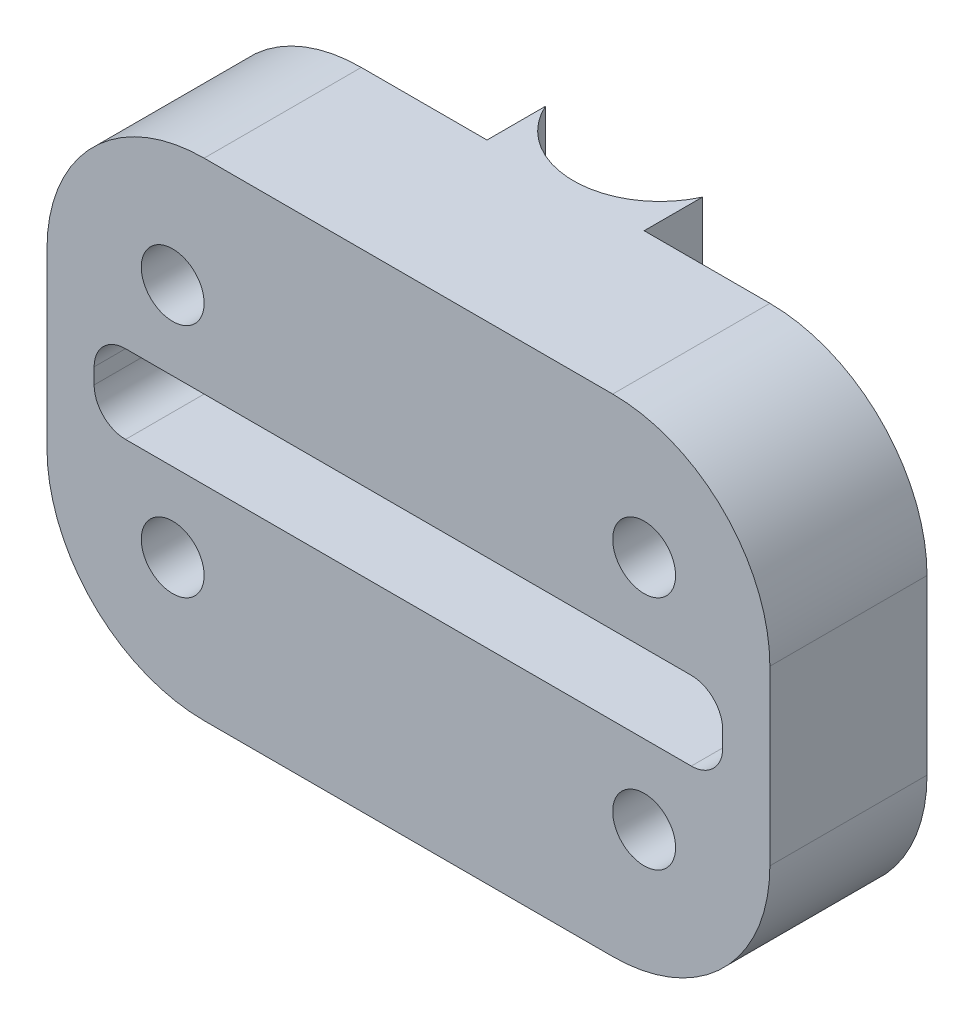
SolidWorks part; units mm, degrees
ref_plane "Front" through (0, 0, 0) normal (0, 0, 1) x (1, 0, 0)
ref_plane "Top" through (0, 0, 0) normal (0, 1, 0) x (1, 0, 0)
ref_plane "Right" through (0, 0, 0) normal (1, 0, 0) x (0, 0, -1)
sketch "Sketch1" plane through (0, 0, 0) normal (0, 0, 1) x (1, 0, 0)
  line L1 (-23, 15.5) -> (23, 15.5)
  line L2 (-23, 15.5) -> (-23, -15.5)
  line L3 (-23, -15.5) -> (23, -15.5)
  line L4 (23, 15.5) -> (23, -15.5)
  line L5 (-23, 15.5) -> (23, -15.5) construction
  line L6 (-23, -15.5) -> (23, 15.5) construction
  line L7 (-15, 7.5) -> (15, 7.5) construction
  line L8 (-15, 7.5) -> (-15, -7.5) construction
  line L9 (-15, -7.5) -> (15, -7.5) construction
  line L10 (15, 7.5) -> (15, -7.5) construction
  line L11 (-15, 7.5) -> (15, -7.5) construction
  line L12 (-15, -7.5) -> (15, 7.5) construction
  circle A0 centre (-15, 7.5) radius 2
  circle A1 centre (15, 7.5) radius 2
  circle A2 centre (15, -7.5) radius 2
  circle A3 centre (-15, -7.5) radius 2
  point P0 (0, 0)
  point P6 (0, 0)
  dimension "D3" = 4
  dimension "D1" = 30
  dimension "D2" = 15
  dimension "D4" = 8
  dimension "D5" = 8
extrude "Boss-Extrude1" add sketch "Sketch1" along normal blind 10
fillet "Fillet1" radius 10 4 edges at (-23, 15.5, 5) (23, 15.5, 5) (23, -15.5, 5) (-23, -15.5, 5)
sketch "Sketch3" plane through (0, 0, 0) normal (0, 1, 0) x (1, 0, 0)
  line L0 (13, 0) -> (-13, 0) construction
  line L1 (-5, 0) -> (5, 0)
  line L2 (-5, 0) -> (-5, 6)
  line L3 (-5, 6) -> (5, 6)
  line L4 (5, 0) -> (5, 6)
  circle A0 centre (0, 6) radius 5.5
  point P6 (0, 6)
  dimension "D1" = 11
  dimension "D2" = 6
  dimension "D3" = 10
extrude "Boss-Extrude2" add sketch "Sketch3" against normal blind 10 from surface contours A0 L3 L2 L1 L4 region at (-4.8933, 0, -1.8544) starting at face at (0, 15.5, 5)
extrude "Boss-Extrude3" add sketch "Sketch3<3>" along normal blind 10 from surface contours A0 L3 L2 L1 L4 region at (-4.8933, 0, -1.8544) starting at face at (0, -15.5, 5)
sketch "Sketch3<3>" plane through (0, 0, 0) normal (0, 1, 0) x (1, 0, 0) same geometry as "Sketch3"
sketch "Sketch4" plane through (0, 0, 0) normal (0, 0, -1) x (-1, 0, 0)
  line L1 (-20, 2.5) -> (20, 2.5)
  line L2 (-20, 2.5) -> (-20, -2.5)
  line L3 (-20, -2.5) -> (20, -2.5)
  line L4 (20, 2.5) -> (20, -2.5)
  line L5 (-20, 2.5) -> (20, -2.5) construction
  line L6 (-20, -2.5) -> (20, 2.5) construction
  point P0 (0, 0)
  dimension "D1" = 5
  dimension "D2" = 40
extrude "Cut-Extrude1" cut sketch "Sketch4" against normal through all both and the other way through all
fillet "Fillet2" radius 2 4 edges at (-20, -2.5, 5) (20, 2.5, 5) (-20, 2.5, 5) (20, -2.5, 5)
equation "\"D5@Sketch1\"=\"D4@Sketch1\""
